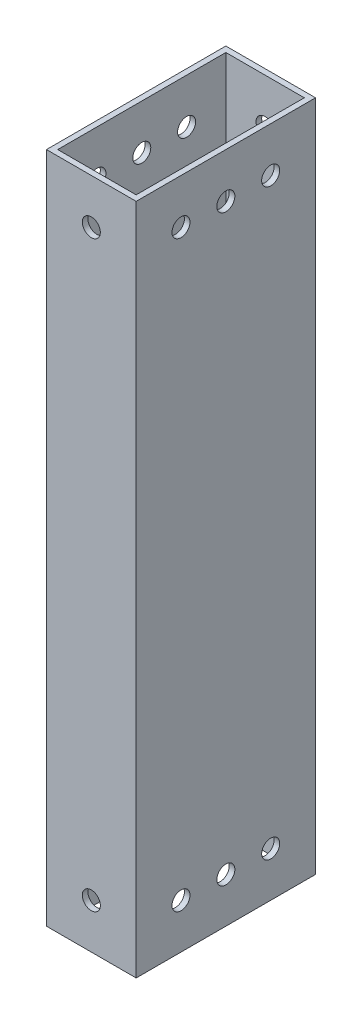
SolidWorks part; units mm, degrees
material "6061-T6 (SS)"
ref_plane "Front" through (0, 0, 0) normal (0, 0, 1) x (1, 0, 0)
ref_plane "Top" through (0, 0, 0) normal (0, 1, 0) x (1, 0, 0)
ref_plane "Right" through (0, 0, 0) normal (1, 0, 0) x (0, 0, -1)
sketch "Sketch1" plane through (0, 0, 0) normal (0, 1, 0) x (1, 0, 0)
  line L1 (12.7, 25.4) -> (-12.7, 25.4)
  line L2 (12.7, 25.4) -> (12.7, -25.4)
  line L3 (12.7, -25.4) -> (-12.7, -25.4)
  line L4 (-12.7, 25.4) -> (-12.7, -25.4)
  line L5 (12.7, 25.4) -> (-12.7, -25.4) construction
  line L6 (12.7, -25.4) -> (-12.7, 25.4) construction
  point P0 (0, 0)
  dimension "D1" = 25.4
  dimension "D2" = 50.8
extrude "Extrude-Thin1" add sketch "Sketch1" along normal up to surface (190.5 mm away) thin thin type one direction reverse wall 1.5875
sketch "Sketch4" plane through (-12.7, 0, 0) normal (-1, 0, 0) x (0, 0, 1)
  line L0 (-12.7, 12.7) -> (12.7, 12.7) construction
  line L3 (-12.7, 177.8) -> (12.7, 177.8) construction
  line L4 (-25.4, 0) -> (25.4, 0) construction
  line L5 (-25.4, 190.5) -> (25.4, 190.5) construction
  point P1 (-12.7, 12.7)
  point P2 (12.7, 12.7)
  point P6 (-12.7, 177.8)
  point P7 (12.7, 177.8)
  point P11 (0, 177.8)
  point P17 (0, 12.7)
  point P27 (-12.7, 177.8)
  point P29 (12.7, 177.8)
  point P31 (-12.7, 12.7)
  point P33 (12.7, 12.7)
  dimension "D1" = 12.7
  dimension "D2" = 12.7
  dimension "D3" = 12.7
hole_wizard "#10 Clearance Hole1" positions "Sketch4" profile "Sketch3" hole size "#10" standard "ANSI Inch" end condition through all
sketch "Sketch3" plane through (-12.7, 12.7, 12.7) normal (0, 1, 0) x (0, 0, 1)
  line L0 (0, 0) -> (0, 25.4)
  line L1 (0, 25.4) -> (2.5527, 25.4)
  line L2 (2.5527, 25.4) -> (2.5527, 0)
  line L5 (2.5527, 0) -> (0, 0)
  line L11 (0, -6.35) -> (0, 107.95) construction
  dimension "Thru Hole Dia." = 5.1054
  dimension "Thru Hole Depth" = 25.4
sketch "Sketch7" plane through (0, 0, 25.4) normal (0, 0, 1) x (1, 0, 0)
  line L0 (-12.7, 0) -> (12.7, 0) construction
  line L1 (-12.7, 190.5) -> (12.7, 190.5) construction
  point P0 (0, 177.8)
  point P2 (0, 12.7)
  dimension "D1" = 12.7
  dimension "D2" = 12.7
hole_wizard "#10 Clearance Hole2" positions "Sketch7" profile "Sketch6" hole size "#10" standard "ANSI Inch" end condition through all
sketch "Sketch6" plane through (0, 177.8, 25.4) normal (1, 0, 0) x (0, -1, 0)
  line L0 (0, 0) -> (0, 50.8)
  line L1 (0, 50.8) -> (2.5527, 50.8)
  line L2 (2.5527, 50.8) -> (2.5527, 0)
  line L5 (2.5527, 0) -> (0, 0)
  line L11 (0, -6.35) -> (0, 107.95) construction
  dimension "Thru Hole Dia." = 5.1054
  dimension "Thru Hole Depth" = 50.8
